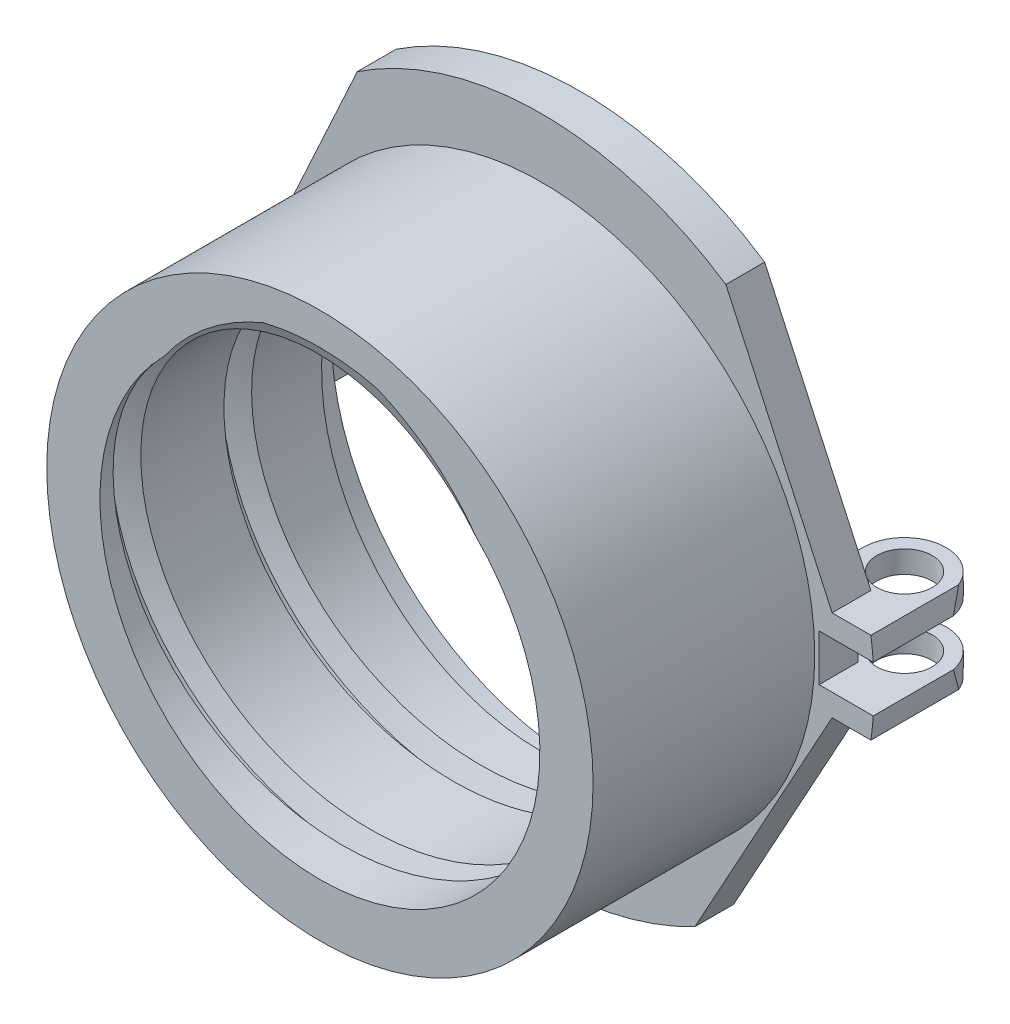
SolidWorks part; units mm, degrees
note: The reader was unsure of these and kept them because the rebuilt part matched: shared geometry of "Sketch13<3>".
ref_plane "Front Plane" through (0, 0, 0) normal (0, 0, 1) x (1, 0, 0)
ref_plane "Top Plane" through (0, 0, 0) normal (0, 1, 0) x (1, 0, 0)
ref_plane "Right Plane" through (0, 0, 0) normal (1, 0, 0) x (0, 0, -1)
sketch "Sketch2" plane through (0, 0, 0) normal (0, 0, 1) x (1, 0, 0)
  circle A0 centre (0, 0) radius 24.65
  circle A1 centre (0, 0) radius 19.85
extrude "Boss-Extrude1" add sketch "Sketch2" along normal blind 20
sketch "Sketch3" plane through (0, 0, 0) normal (0, 0, -1) x (-1, 0, 0)
  circle A0 centre (0, 0) radius 30
  circle A1 centre (0, 0) radius 22.5
extrude "Boss-Extrude2" add sketch "Sketch3" along normal blind 3.5
sketch "Sketch11" plane through (0, 0, 20) normal (0, 0, 1) x (1, 0, 0)
  circle A0 centre (0, 0) radius 19.85 construction
  circle A1 centre (0, 0) radius 19.85
curve "Helix/Spiral1" pitch 10 height 20 radius 19.85 left hand yes centre (0, 0, 20) axis (0, 0, -1) start towards (0, 1, 0)
sketch "Sketch12" plane through (0, 0, 0) normal (1, 0, 0) x (0, 0, -1)
  line L0 (-21.25, 19.85) -> (-18.75, 19.85)
  line L4 (-18.75, 19.85) -> (-19.625, 21.7264)
  line L5 (-19.625, 21.7264) -> (-20.375, 21.7264)
  line L6 (-20.375, 21.7264) -> (-21.25, 19.85)
  point P2 (-20, 19.85)
  dimension "D1" = 2.5
  dimension "D2" = 65
  dimension "D3" = 65
  dimension "D4" = 0.75
sweep "Cut-Sweep1" cut profiles "Sketch12" path "Helix/Spiral1" align with end faces yes
sketch "Sketch13" plane through (0, 0, 0) normal (0, 1, 0) x (1, 0, 0)
  line L0 (-22.5, 6.5) -> (-22.5, 3.5)
  line L1 (-30, 3.5) -> (-30, 6.5)
  line L2 (-30, 3.5) -> (-22.5, 3.5)
  line L3 (0, 19.2862) -> (0, 0)
  line L4 (30, 3.5) -> (22.5, 3.5)
  line L5 (30, 3.5) -> (30, 6.5)
  line L6 (22.5, 6.5) -> (22.5, 3.5)
  arc A0 (-22.5, 6.5) -> (-30, 6.5) centre (-26.25, 6.5) ccw
  circle A1 centre (-26.25, 6.5) radius 2.5
  circle A2 centre (26.25, 6.5) radius 2.5
  arc A3 (22.5, 6.5) -> (30, 6.5) centre (26.25, 6.5) cw
  dimension "D1" = 5
  dimension "D2" = 3
  dimension "D3" = 7.5
extrude "Boss-Extrude3" add sketch "Sketch13" along normal blind 2 from offset 2.1 contours A3 L6 L4 L5 A2
extrude "Boss-Extrude4" add sketch "Sketch13<3>" against normal blind 2 from offset 2.1 contours A3 L6 L4 L5 A2 offset against normal yes
sketch "Sketch13<3>" plane through (0, 0, 0) normal (0, 1, 0) x (1, 0, 0) same geometry as "Sketch13"
mirror "Mirror1" about plane through (0, 0, 0) normal (1, 0, 0) of "Boss-Extrude4", "Boss-Extrude3"
sketch "Sketch16" plane through (0, 0, -3.5) normal (0, 0, -1) x (-1, 0, 0)
  circle A0 centre (0, 0) radius 30
  circle A1 centre (0, 0) radius 30.2789
extrude "Cut-Extrude1" cut sketch "Sketch16" along normal through all
sketch "Sketch20" plane through (0, 0, 0) normal (0, 0, 1) x (1, 0, 0)
  line L8 (29.7185, 4.1) -> (26.2185, 4.1)
  line L10 (16.6306, 24.9685) -> (29.7185, 24.9685)
  line L11 (29.7185, 24.9685) -> (29.7185, 4.1)
  line L12 (29.7185, -4.1) -> (26.2185, -4.1)
  line L14 (13.8346, -26.6196) -> (29.7185, -26.6196)
  line L15 (29.7185, -26.6196) -> (29.7185, -4.1)
  line L22 (25.0412, 2.1) -> (29.9264, 2.1)
  line L24 (26.2185, 4.1) -> (16.6306, 24.9685)
  line L25 (26.2185, -4.1) -> (13.8346, -26.6196)
  line L26 (26.2185, -2.1) -> (29.9264, -2.1)
  line L27 (25.0412, 2.1) -> (25.0412, -2.1)
  line L28 (25.0412, -2.1) -> (26.2185, -2.1)
  arc A0 (29.9264, -2.1) -> (29.9264, 2.1) centre (0, 0) ccw construction
  circle A1 centre (0, 0) radius 30 construction
  arc A3 (29.9264, -2.1) -> (29.9264, 2.1) centre (0, 0) ccw
  dimension "D1" = 8.2
  dimension "D2" = 3.5
  dimension "D3" = 3.5
  dimension "D4" = 4.2
extrude "Cut-Extrude2" cut sketch "Sketch20" against normal through all
mirror "Mirror2" about plane through (0, 0, 0) normal (1, 0, 0) of "Cut-Extrude2"
